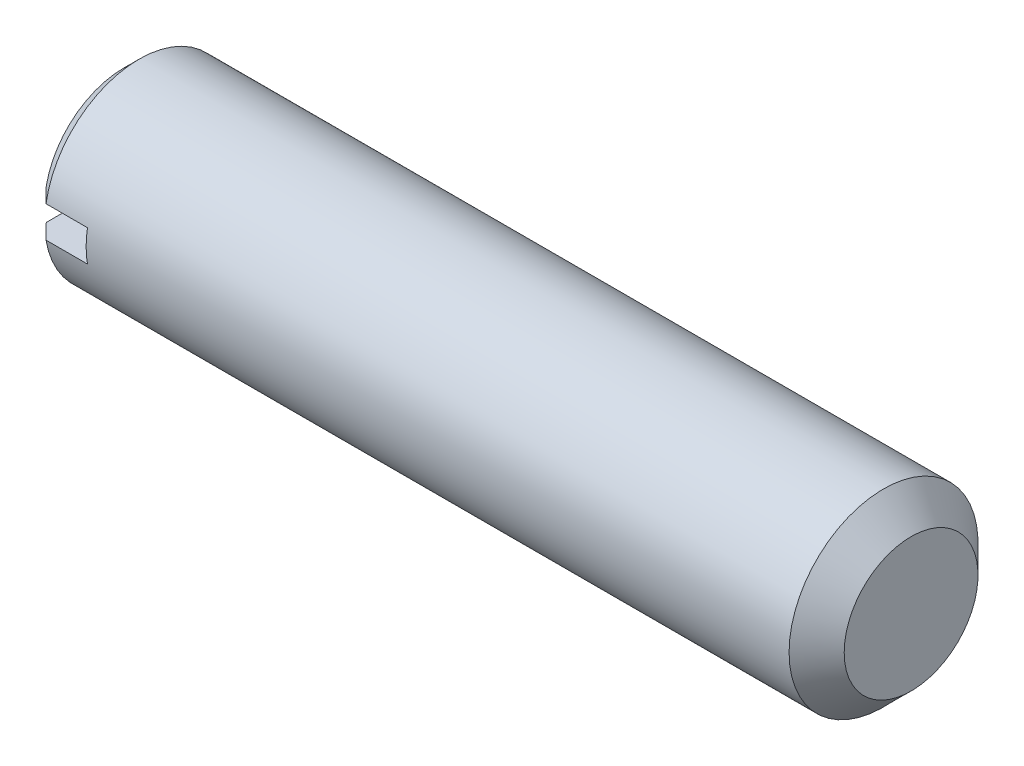
SolidWorks part; units mm, degrees
ref_plane "Front Plane" through (0, 0, 0) normal (0, 0, 1) x (1, 0, 0)
ref_plane "Top Plane" through (0, 0, 0) normal (0, 1, 0) x (1, 0, 0)
ref_plane "Right Plane" through (0, 0, 0) normal (1, 0, 0) x (0, 0, -1)
sketch "BodySke" plane through (0, 0, 0) normal (0, 0, 1) x (1, 0, 0)
  line L0 (0, 0) -> (88.3411, 0) construction
  line L1 (0, 0) -> (0, 5.036)
  line L2 (0, 5.036) -> (0.964, 6)
  line L3 (0.964, 6) -> (48.25, 6)
  line L4 (50, 4.25) -> (48.25, 6)
  line L5 (50, 4.25) -> (50, 0)
  line L6 (50, 0) -> (0, 0)
  line L7 (1.75, 0) -> (1.75, 8.5388) construction
  line L8 (0, -5.036) -> (0.964, -6) construction
  dimension "Thread_minor" = 10.072
  dimension "Drive_chamfer_angle" = 90
  dimension "Advance" = 1.75
revolve "BaseBody" add sketch "BodySke" angle 360 about L0
cosmetic thread "ThreadCosmetic" [suppressed] parameters "Thread_minor"=10.072
sketch "SlotSke" plane through (0, 0, 0) normal (1, 0, 0) x (0, 0, -1)
  line L0 (-6, 1) -> (6, -1) construction
  line L1 (-6, 1) -> (6, 1)
  line L2 (-6, 1) -> (-6, -1)
  line L3 (-6, -1) -> (6, -1)
  line L4 (6, 1) -> (6, -1)
  dimension "D1" = 12
extrude "Slot" cut sketch "SlotSke" along normal blind 3.6
sketch "ThdSchSke" plane through (0, 0, 0) normal (0, 0, 1) x (1, 0, 0)
  line L0 (0, 0) -> (53.6961, 0) construction
  line L1 (1.6009, 7.1131) -> (1.6009, 6)
  line L2 (1.6009, 7.1131) -> (2.714, 7.1131)
  line L3 (2.714, 7.1131) -> (2.714, 6)
  line L4 (2.714, 6) -> (2.1574, 5.036)
  line L5 (2.1574, 5.036) -> (1.6009, 6)
  dimension "D1" = 1.75
revolve "ThreadSchematic" [suppressed] cut sketch "ThdSchSke" angle 360 about L0
pattern_linear "ThdSchPat" [suppressed] of bodies 115
equation "\"Thread_minor@ThreadCosmetic\" = \"Thread_minor@BodySke\""
equation "\"D1@SlotSke\" = \"Diameter@BodySke\""
equation "\"D1@ThdSchSke\" = \"Advance@BodySke\""
equation "\"Advance@ThdSchPat\" = \"Advance@BodySke\""
equation "\"Tooth_Num@ThdSchPat\" =  int( \"Length@BodySke\" / \"Advance@BodySke\" )  - 1"
